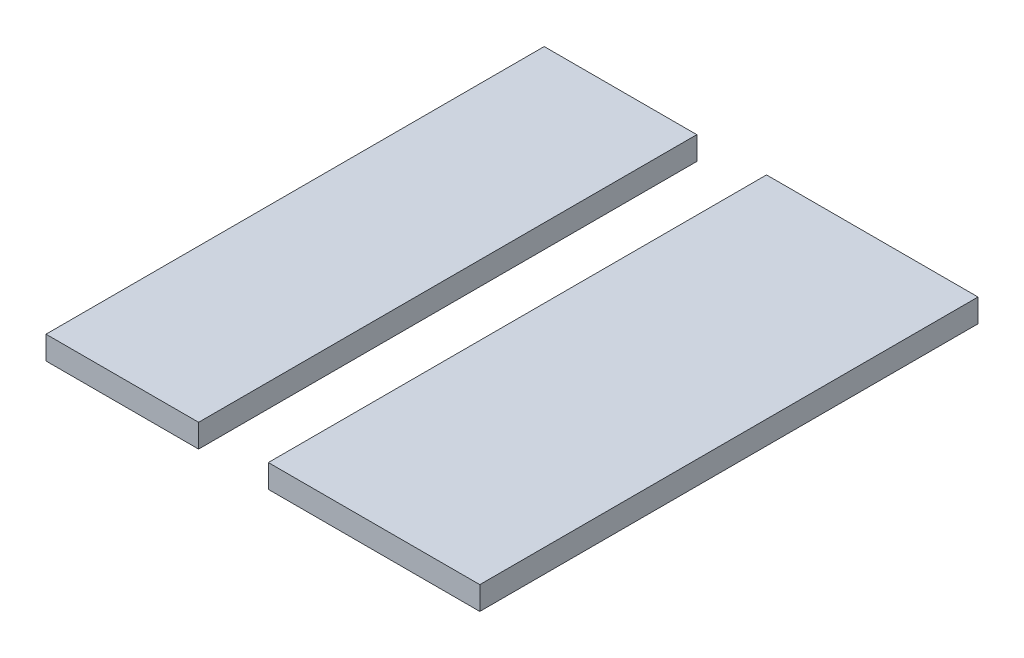
SolidWorks part; units mm, degrees
ref_plane "Front Plane" through (0, 0, 0) normal (0, 0, 1) x (1, 0, 0)
ref_plane "Top Plane" through (0, 0, 0) normal (0, 1, 0) x (1, 0, 0)
ref_plane "Right Plane" through (0, 0, 0) normal (1, 0, 0) x (0, 0, -1)
sketch "Sketch1" plane through (0, 0, 0) normal (0, 1, 0) x (1, 0, 0)
  line L0 (0.7, -32.157) -> (0.7, 32.157)
  line L1 (-28.7, -32.157) -> (28.7, -32.157) construction
  line L2 (-28.7, -32.157) -> (-28.7, 32.157) construction
  line L3 (-28.7, 32.157) -> (28.7, 32.157) construction
  line L4 (28.7, -32.157) -> (28.7, 32.157) construction
  line L5 (-8.3, 32.157) -> (-8.3, -32.157)
  line L6 (28, -32.157) -> (28, 32.157)
  line L7 (-28, -32.157) -> (-28, 32.157)
  line L8 (0, -32.157) -> (0, 32.157) construction
  line L9 (0.7, -32.157) -> (28, -32.157)
  line L10 (28, 32.157) -> (0.7, 32.157)
  line L11 (-8.3, 32.157) -> (-28, 32.157)
  line L12 (-8.3, -32.157) -> (-28, -32.157)
  line L13 (28.7, 0) -> (28, 0) construction
  line L14 (28, 20) -> (28.7, 20) construction
sketch "Sketch2" plane through (0, 0, 0) normal (0, 0, 1) x (1, 0, 0)
  line L0 (0.7, 0) -> (28, 0) construction
  line L1 (28, 0) -> (0.7, 0)
  line L2 (28, 0) -> (28, 3)
  line L3 (28, 3) -> (0.7, 3)
  line L4 (0.7, 0) -> (0.7, 3)
  line L5 (28.7, 3) -> (0.7, 3) construction
  line L7 (-8.3, 3) -> (-28, 3)
  line L8 (-8.3, 3) -> (-8.3, 0)
  line L9 (-8.3, 0) -> (-28, 0)
  line L10 (-28, 3) -> (-28, 0)
extrude "Boss-Extrude1" add sketch "Sketch1" along normal up to vertex (3 mm away) up to point (-28, 3, 0)
